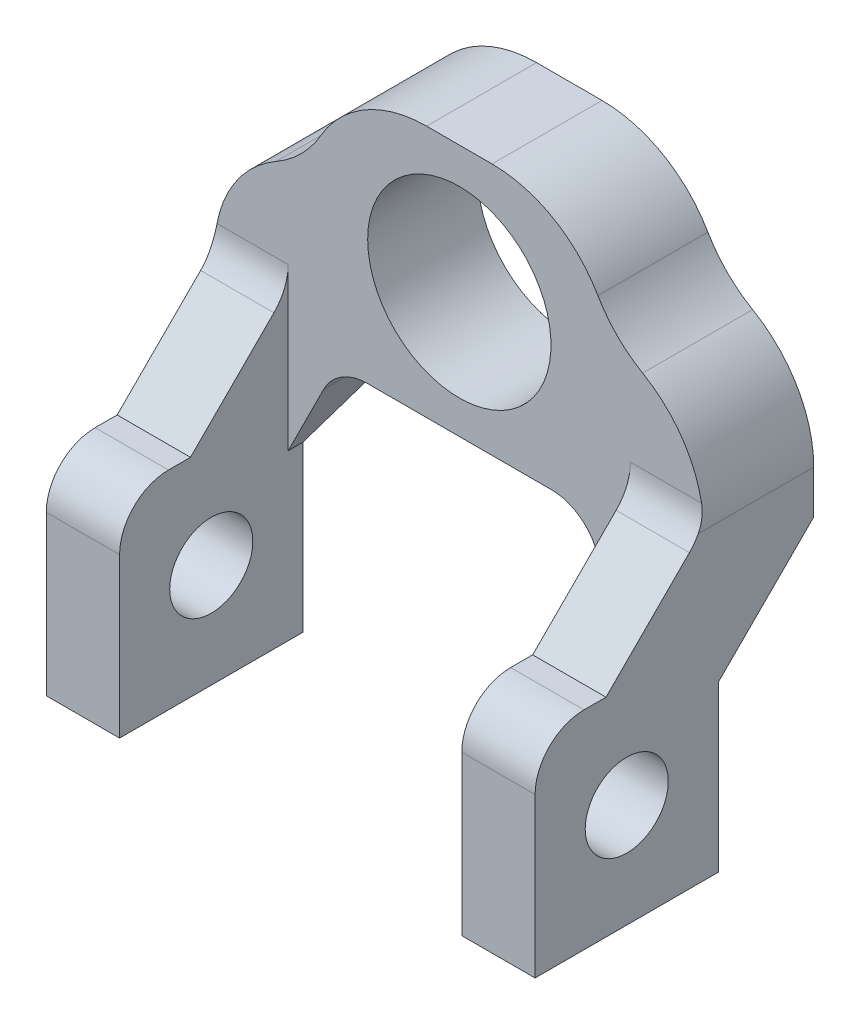
SolidWorks part; units mm, degrees
ref_plane "Alzado" through (0, 0, 0) normal (0, 0, 1) x (1, 0, 0)
ref_plane "Planta" through (0, 0, 0) normal (0, 1, 0) x (1, 0, 0)
ref_plane "Vista lateral" through (0, 0, 0) normal (1, 0, 0) x (0, 0, -1)
sketch "Croquis1" plane through (0, 0, 0) normal (1, 0, 0) x (0, 0, -1)
  line L0 (5.4, 16.814) -> (5.4, -4.8468) construction
  line L1 (-3.75, 4.25) -> (-0.85, 4.25)
  line L2 (-3.75, 4.25) -> (-3.75, -4.25)
  line L3 (-3.75, -4.25) -> (3.75, -4.25)
  line L4 (3.75, 2.486) -> (3.75, -4.25)
  line L5 (-3.75, 4.25) -> (3.75, -4.25) construction
  line L6 (-3.75, -4.25) -> (3.75, 4.25) construction
  line L8 (3.15, 8.25) -> (3.15, 16.814)
  line L9 (3.15, 16.814) -> (7.65, 16.814)
  line L10 (7.65, 6.386) -> (7.65, 16.814)
  line L12 (-0.85, 4.25) -> (3.15, 8.25)
  line L13 (-0.85, 4.25) -> (3.75, 4.25) construction
  line L14 (3.75, 4.25) -> (3.75, 2.486) construction
  line L15 (3.75, 2.486) -> (7.65, 6.386)
  circle A0 centre (5.4, -29) radius 37.1 construction
  circle A1 centre (5.4, -29) radius 24.75 construction
  circle A2 centre (5.4, 11.6) radius 3.5 construction
  point P0 (0, 0)
  point P6 (3.15, 4.25)
  point P16 (7.65, 11.6)
  dimension "D6" = 74.2
  dimension "D7" = 49.5
  dimension "D8" = 7
  dimension "D1" = 4.5
  dimension "D2" = 7.5
  dimension "D3" = 6.9
  dimension "D4" = 8.5
  dimension "D5" = 4.5
extrude "Saliente-Extruir1" add sketch "Croquis1" along normal blind 20
sketch "Croquis2" plane through (0, -4.25, 0) normal (0, -1, 0) x (1, 0, 0)
  line L0 (20, 3.75) -> (0, 3.75) construction
  line L1 (3, 3.75) -> (17, 3.75)
  line L2 (3, 3.75) -> (3, -3.75)
  line L3 (3, -3.75) -> (17, -3.75)
  line L4 (17, 3.75) -> (17, -3.75)
  line L5 (20, -3.75) -> (0, -3.75) construction
  line L6 (0, 0) -> (20, 0) construction
  line L7 (20, 3.75) -> (20, -3.75) construction
  line L8 (10, 0) -> (10, 5.8604) construction
  point P14 (10, 0)
  point P15 (10, 3.75)
  point P17 (10, -3.75)
  dimension "D1" = 14
extrude "Cortar-Extruir1" cut sketch "Croquis2" against normal up to vertex (6.736 mm away) up to point (0, 2.486, -3.75)
sketch "Croquis3" plane through (0, 0, 0) normal (-1, 0, 0) x (0, 0, 1)
  circle A0 centre (0, 0) radius 1.7
  dimension "D1" = 3.4
extrude "Cortar-Extruir2" cut sketch "Croquis3" against normal up to surface (20 mm away) up to face at (20, 5.6389, -2.3056)
sketch "Croquis5" plane through (0, 0, -3.15) normal (0, 0, 1) x (1, 0, 0)
  line L0 (20, 8.25) -> (0, 8.25) construction
  line L1 (3, 2.486) -> (17, 2.486)
  line L2 (3, 2.486) -> (3, 8.25)
  line L3 (3, 8.25) -> (17, 8.25)
  line L4 (17, 2.486) -> (17, 8.25)
  line L5 (17, 2.486) -> (17, -4.25) construction
extrude "Cortar-Extruir4" cut sketch "Croquis5" along normal blind 10
sketch "Croquis4" plane through (0, 0, -7.65) normal (0, 0, -1) x (-1, 0, 0)
  line L0 (-20, 11.814) -> (-15, 11.814)
  line L2 (-15, 11.814) -> (-15, 16.814)
  line L3 (-20, 16.814) -> (0, 16.814) construction
  line L4 (-15, 16.814) -> (-20, 16.814)
  line L5 (-20, 16.814) -> (-20, 11.814)
  line L6 (-10, 14.7) -> (-10, 9.5322) construction
  line L7 (-5, 16.814) -> (0, 16.814)
  line L8 (0, 16.814) -> (0, 11.814)
  line L9 (0, 11.814) -> (-5, 11.814)
  line L10 (-5, 11.814) -> (-5, 16.814)
  line L11 (0, 11.6) -> (-10, 11.6) construction
  line L12 (0, 6.386) -> (0, 16.814) construction
  line L15 (-15, 6.486) -> (-5, 6.486)
  line L20 (-15, 6.486) -> (-17, 2.486)
  line L21 (-17, 2.486) -> (-3, 2.486)
  line L22 (-3, 2.486) -> (-5, 6.486)
  circle A1 centre (-10, 11.6) radius 3.75
  point P16 (0, 0)
  point P21 (0, 0)
  point P24 (-10, 6.486)
  point P25 (0, 0)
  dimension "D1" = 7.5
  dimension "D2" = 5
  dimension "D3" = 5
  dimension "D4" = 4
  dimension "D5" = 10
extrude "Cortar-Extruir3" cut sketch "Croquis4" against normal up to surface (4.5 mm away) up to face at (10, 8.95, -3.15)
fillet "Redondeo1" radius 5 2 edges at (5, 11.814, -5.4) (15, 11.814, -5.4)
fillet "Redondeo2" radius 5 4 edges at (15, 16.814, -5.4) (5, 16.814, -5.4) (20, 11.814, -5.4) (0, 11.814, -5.4)
fillet "Redondeo3" radius 2 6 edges at (15, 6.486, -5.4) (5, 6.486, -5.4) (1.5005, 8.25, -3.15) (18.4995, 8.25, -3.15) (18.5, 4.25, 3.75) (1.5, 4.25, 3.75)
